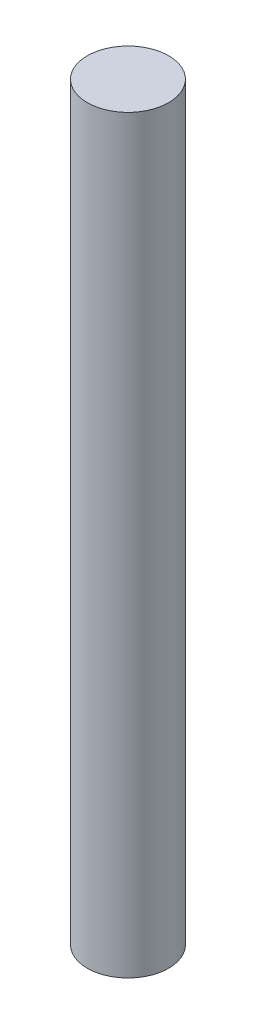
SolidWorks part; units mm, degrees
ref_plane "Front Plane" through (0, 0, 0) normal (0, 0, 1) x (1, 0, 0)
ref_plane "Top Plane" through (0, 0, 0) normal (0, 1, 0) x (1, 0, 0)
ref_plane "Right Plane" through (0, 0, 0) normal (1, 0, 0) x (0, 0, -1)
sketch "Sketch1" plane through (0, 0, 0) normal (0, 1, 0) x (1, 0, 0)
  circle A0 centre (0, 0) radius 0.5
extrude "Boss-Extrude1" add sketch "Sketch1" along normal blind 9.22
